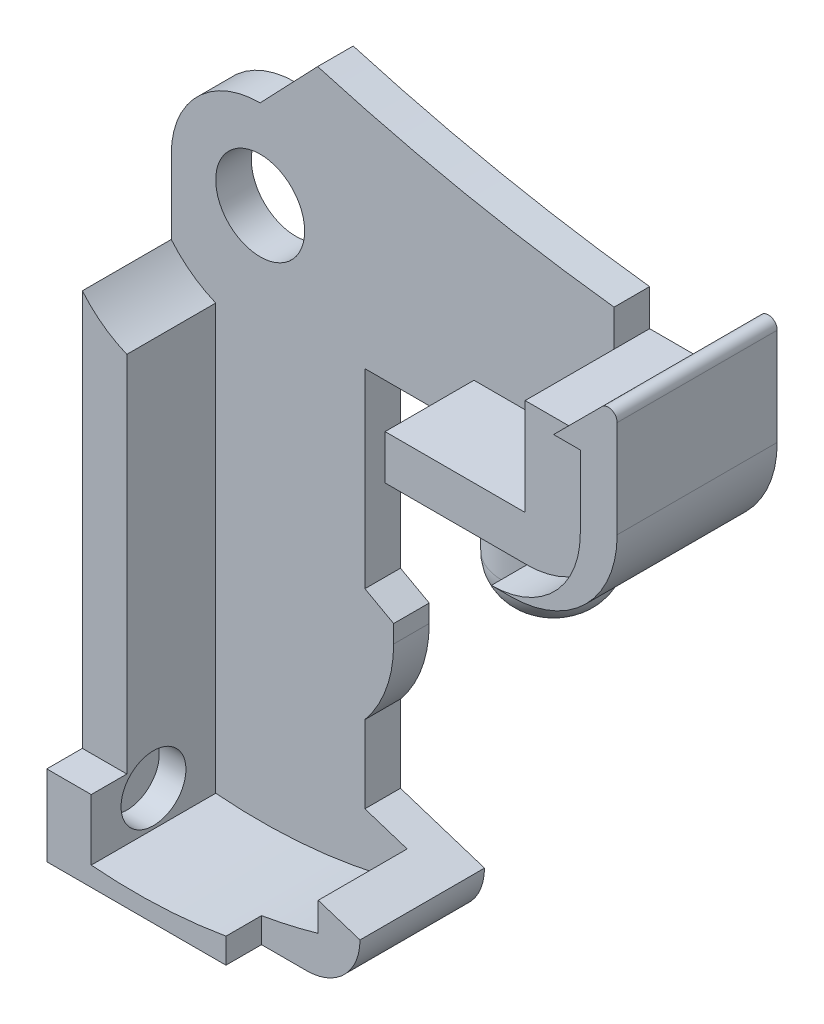
SolidWorks part; units mm, degrees
ref_plane "정면" through (0, 0, 0) normal (0, 0, 1) x (1, 0, 0)
ref_plane "윗면" through (0, 0, 0) normal (0, 1, 0) x (1, 0, 0)
ref_plane "우측면" through (0, 0, 0) normal (1, 0, 0) x (0, 0, -1)
sketch "스케치1" plane through (0, 0, 0) normal (0, 0, 1) x (1, 0, 0)
  line L0 (0, 5) -> (3.2319, 8.3833)
  line L1 (0, 5) -> (19.9, 5)
  line L2 (19.9, 5) -> (19.9, 2.9507)
  line L3 (19.9, 2.9507) -> (23.5, 2.9507)
  line L4 (23.5, 2.9507) -> (23.5, 4.0959)
  line L5 (23.5, 4.0959) -> (25, 4.0959)
  line L6 (25, 4.0959) -> (25, 0)
  line L7 (20, -5) -> (5.8894, -5)
  line L8 (5.8894, -5) -> (5.8894, -26.4376)
  line L9 (-5, -30.9618) -> (7.6137, -30.9618)
  line L10 (-5, -30.9618) -> (-5, 0)
  line L14 (19.9, 2.9507) -> (19.9, -2.5)
  line L15 (19.9, -2.5) -> (12.0232, -2.5)
  line L16 (-2.5, -4.3301) -> (-2.5, -26.4377)
  line L17 (-2.5, -29.8745) -> (-2.5, -26.4377)
  line L18 (-2.5, -26.4377) -> (-5, -26.4377)
  line L19 (5.0761, -29.546) -> (5.0761, -30.9618)
  line L20 (5.8894, -15.7188) -> (5.8894, -26.4376)
  line L21 (8.2649, -27.204) -> (8.2649, -28.8171)
  line L22 (12.0232, -2.5) -> (12.0232, -5)
  line L23 (5.8894, -15.7188) -> (5.8894, -26.4376)
  line L24 (7.5062, -17.6039) -> (7.5062, -16.6061)
  line L25 (7.5062, -16.6061) -> (5.8894, -15.7188)
  line L26 (23.5, 4.0959) -> (26.2222, 6.8181)
  line L27 (27.0757, 6.4645) -> (27.0757, 1)
  line L28 (21.0757, -5) -> (20, -5)
  line L29 (10.6137, -27.9618) -> (5.8894, -26.4376)
  circle A0 centre (0, 0) radius 2.5
  circle A1 centre (0, 0) radius 5
  arc A2 (-2.5, -29.8745) -> (8.2649, -28.8171) centre (0, 0) ccw
  arc A3 (-5, -4.1533) -> (-2.5, -6) centre (0, 0) ccw
  arc A4 (19.9, 5) -> (3.2319, 8.3833) centre (32.0341, 107.5303) cw
  arc A5 (25, 0) -> (20, -5) centre (20, 0) cw
  arc A6 (7.5062, -17.6039) -> (5.8894, -22.0908) centre (0.4717, -17.6039) cw
  arc A7 (7.6137, -30.9618) -> (10.6137, -27.9618) centre (7.6137, -27.9618) ccw
  arc A8 (27.0757, 1) -> (21.0757, -5) centre (21.0757, 1) cw
  arc A9 (26.2222, 6.8181) -> (27.0757, 6.4645) centre (26.5757, 6.4645) cw
  point P48 (27.0757, 7.6716)
  dimension "D1" = 5
  dimension "D3" = 5
  dimension "D6" = 3
  dimension "D9" = 6
  dimension "D10" = 0.5
  dimension "D4" = 30
  dimension "D5" = 1.5
  dimension "D7" = 5.0568
  dimension "D8" = 45
  dimension "D11" = 3.6
  dimension "D12" = 32.0757
extrude "보스-돌출3" add sketch "스케치1" along normal blind 9 contours A2 L17 L18 L10 L9 L19 | A9 L26 L5 L6 A5 L28 A8 L27 region at (-3.75, -26.5481, 0) region at (25.5751, 1.3496, 0)
extrude "보스-돌출4" add sketch "스케치1<7>" along normal blind 7 contours A2 L19 L9 | L15 L7 L6 L5 L4 L3 L14 | A1 L10 L18 L16 region at (20.1111, -1.5639, 0) region at (-3.7678, -15.8289, 0) region at (8.0449, -29.4837, 0)
sketch "스케치1<7>" plane through (0, 0, 0) normal (0, 0, 1) x (1, 0, 0) same geometry as "스케치1"
extrude "보스-돌출5" add sketch "스케치1<8>" along normal blind 2 contours L17 A2 L8 L15 L14 L2 L1 A1 L10 L18 | A1 A0 | L10 A3 L16 A1 | L1 A4 L0 | A6 L23 region at (7.1976, 6.0706, 0) region at (5.5582, -10.4694, 0) region at (3.4355, 3.4355, 0) region at (-3.8947, -3.9886, 0) region at (6.5659, -18.5308, 0)
sketch "스케치1<8>" plane through (0, 0, 0) normal (0, 0, 1) x (1, 0, 0) same geometry as "스케치1"
sketch "스케치2" plane through (0, -5, 0) normal (0, -1, 0) x (1, 0, 0)
  circle A0 centre (18, 3.5) radius 2.9
  dimension "D1" = 5.8
extrude "보스-돌출6" add sketch "스케치2" along normal mid plane 4.9
sketch "스케치4" plane through (0, -7.45, 0) normal (0, -1, 0) x (1, 0, 0)
  circle A0 centre (18, 3.5) radius 2.9 construction
  circle A1 centre (18, 3.5) radius 2.9
extrude "보스-돌출7" add sketch "스케치4" along normal blind 2
fillet "필렛2" radius 2.4 1 edges at (18, -9.45, 0.6)
sketch "스케치5" plane through (-2.5, 0, 0) normal (1, 0, 0) x (0, 0, -1)
  line L0 (-9, -29.8745) -> (-2, -29.8745) construction
  circle A0 centre (-5.5, -27.8745) radius 1.825
  point P2 (-5.5, -29.8745)
  dimension "D1" = 3.65
  dimension "D2" = 2
extrude "컷-돌출1" cut sketch "스케치5" against normal blind 1.5
